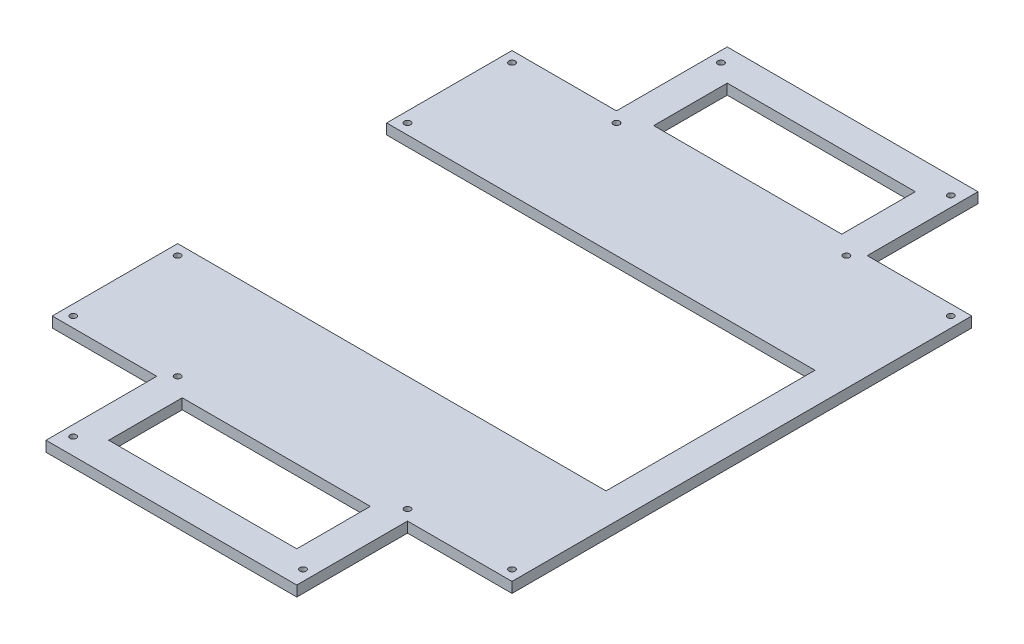
SolidWorks part; units mm, degrees
ref_plane "Plan de face" through (0, 0, 0) normal (0, 0, 1) x (1, 0, 0)
ref_plane "Plan de dessus" through (0, 0, 0) normal (0, 1, 0) x (1, 0, 0)
ref_plane "Plan de droite" through (0, 0, 0) normal (1, 0, 0) x (0, 0, -1)
sketch "Esquisse1" plane through (0, 0, 0) normal (0, 1, 0) x (1, 0, 0)
  line L0 (-60, 110) -> (-60, 163)
  line L1 (110, -110) -> (60, -110)
  line L2 (110, -110) -> (110, 110)
  line L3 (110, 110) -> (60, 110)
  line L4 (-110, -110) -> (-110, -50)
  line L5 (110, -110) -> (-110, 110) construction
  line L6 (110, 110) -> (-110, -110) construction
  line L7 (-60, 163) -> (60, 163)
  line L8 (60, 163) -> (60, 110)
  line L9 (0, 163) -> (0, -89.8749) construction
  line L10 (-108.9276, 0) -> (110, 0) construction
  line L11 (-105, -105) -> (-105, -50) construction
  line L12 (-55, -105) -> (-55, -163) construction
  line L13 (-60, 110) -> (-110, 110)
  line L14 (60, -163) -> (60, -110)
  line L15 (-60, -163) -> (60, -163)
  line L16 (-60, -110) -> (-60, -163)
  line L17 (-60, -110) -> (-110, -110)
  line L18 (45, -148) -> (-45, -148)
  line L19 (45, 112.8) -> (-45, 112.8)
  line L20 (45, 112.8) -> (45, 148)
  line L21 (45, 148) -> (-45, 148)
  line L22 (-45, 112.8) -> (-45, 148)
  line L23 (45, 112.8) -> (-45, 148) construction
  line L24 (45, 148) -> (-45, 112.8) construction
  line L25 (-45, -112.8) -> (-45, -148)
  line L26 (45, -112.8) -> (-45, -112.8)
  line L27 (45, -112.8) -> (45, -148)
  line L28 (-110, 50) -> (-110, 110)
  line L29 (95, -50) -> (-110, -50)
  line L30 (95, -50) -> (95, 50)
  line L31 (95, 50) -> (-110, 50)
  line L33 (-105, -105) -> (105, -105) construction
  line L34 (105, -105) -> (105, 0) construction
  line L35 (-60, 112.8) -> (60, 112.8) construction
  line L36 (-55, 105) -> (-55, 155) construction
  line L37 (-55, 155) -> (55, 155) construction
  line L38 (55, 155) -> (55, 105) construction
  line L39 (55, 105) -> (55, 155) construction
  circle A0 centre (-105, -105) radius 1.5
  circle A1 centre (-105, -55) radius 1.5
  circle A2 centre (-55, -105) radius 1.5
  circle A5 centre (-5, -105) radius 1.5 [skipped]
  circle A6 centre (45, -105) radius 1.5 [skipped]
  circle A7 centre (-55, -155) radius 1.5
  circle A9 centre (-55, 105) radius 1.5
  circle A10 centre (-105, 105) radius 1.5
  circle A11 centre (-105, 55) radius 1.5
  circle A12 centre (55, -155) radius 1.5
  circle A13 centre (55, -105) radius 1.5
  circle A14 centre (105, -105) radius 1.5
  circle A15 centre (105, 105) radius 1.5
  circle A16 centre (55, 105) radius 1.5
  circle A18 centre (-55, 155) radius 1.5
  circle A19 centre (55, 155) radius 1.5
  point P0 (0, 0)
  point P23 (0, 130.4)
  point P28 (-45, 130.4)
  point P33 (0.5362, 0)
  dimension "D4" = 3
  dimension "D6" = 53
  dimension "D14" = 5
  dimension "D16" = 8
  dimension "D1" = 220
  dimension "D2" = 50
  dimension "D3" = 50
  dimension "D5" = 5
  dimension "D7" = 2
  dimension "D8" = 15
  dimension "D9" = 15
  dimension "D10" = 15
  dimension "D11" = 60
  dimension "D13" = 2
  dimension "D12" = 60
  dimension "D18" = 120
  dimension "D20" = 50
  dimension "D15" = 4
  dimension "D17" = 2
  dimension "D19" = 2
extrude "Boss.-Extru.1" add sketch "Esquisse1" along normal blind 5
